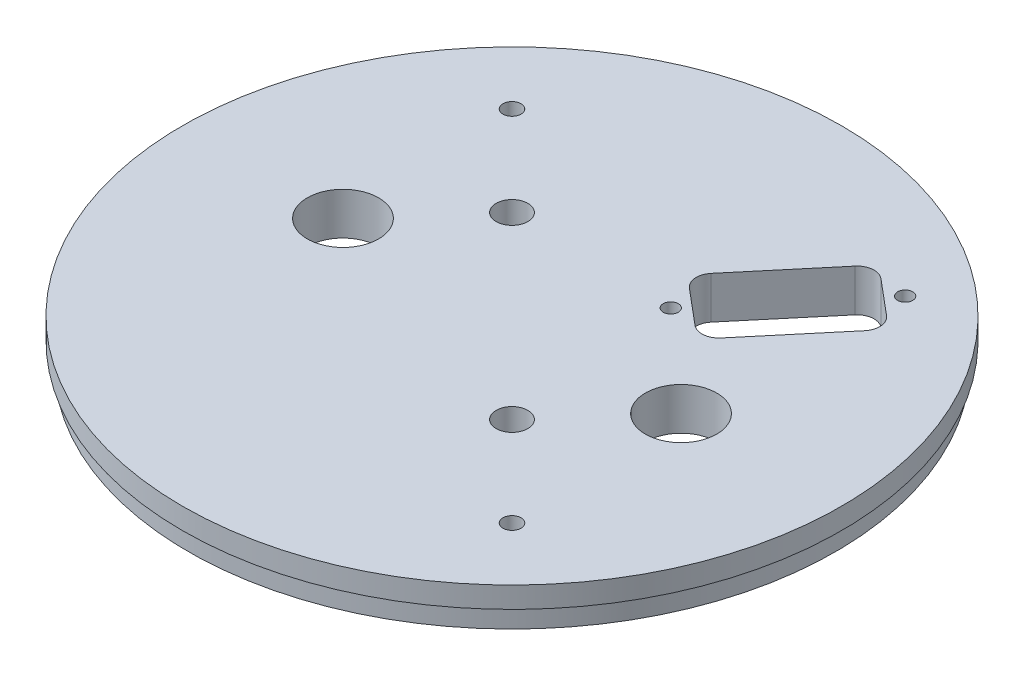
SolidWorks part; units mm, degrees
material "6061-T6 (SS)"
ref_plane "Front Plane" through (0, 0, 0) normal (0, 0, 1) x (1, 0, 0)
ref_plane "Top Plane" through (0, 0, 0) normal (0, 1, 0) x (1, 0, 0)
ref_plane "Right Plane" through (0, 0, 0) normal (1, 0, 0) x (0, 0, -1)
sketch "Sketch1" plane through (0, 0, 0) normal (0, 1, 0) x (1, 0, 0)
  line L0 (0, -49.5173) -> (0, 49.5173) construction
  line L1 (-49.5173, 0) -> (49.5173, 0) construction
  line L2 (-26.9408, 26.9408) -> (0, 0) construction
  line L3 (0, 56.7387) -> (0, 29.6936) construction
  line L4 (3.6407, 56.7387) -> (3.6407, 29.6936) construction
  line L5 (-3.6407, 56.7387) -> (-3.6407, 29.6936) construction
  line L6 (0, -56.7387) -> (0, -29.6936) construction
  line L7 (3.6407, -56.7387) -> (3.6407, -29.6936) construction
  line L8 (-3.6407, -56.7387) -> (-3.6407, -29.6936) construction
  line L9 (-35.014, -35.014) -> (54.3236, 54.3236) construction
  circle A0 centre (0, 0) radius 49.5173
  circle A1 centre (0, 0) radius 3.175 construction
  circle A2 centre (25.4, 0) radius 5.3578
  circle A3 centre (-25.4, 0) radius 5.3578
  circle A4 centre (-26.9408, 26.9408) radius 1.3589
  arc A6 (3.6407, 56.7387) -> (-3.6407, 56.7387) centre (0, 56.7387) ccw construction
  arc A7 (-3.6407, 29.6936) -> (3.6407, 29.6936) centre (0, 29.6936) ccw construction
  arc A8 (3.6407, -56.7387) -> (-3.6407, -56.7387) centre (0, -56.7387) cw construction
  arc A9 (-3.6407, -29.6936) -> (3.6407, -29.6936) centre (0, -29.6936) cw construction
  circle A10 centre (26.9408, -26.9408) radius 1.3589
  circle A11 centre (-13.4704, 13.4704) radius 2.3813
  circle A12 centre (13.4704, -13.4704) radius 2.3813
  point P16 (0, 43.2162)
  point P19 (0, 0)
  point P26 (0, -43.2162)
  dimension "D1" = 99.0346
  dimension "D2" = 6.35
  dimension "D3" = 10.7156
  dimension "D5" = 2.7178
  dimension "D8" = 4.7625
  dimension "D6" = 38.1
  dimension "D7" = 45
  dimension "D4" = 45
  dimension "D9" = 25.4
extrude "Boss-Extrude1" add sketch "Sketch1" along normal blind 6.35
sketch "Sketch2" plane through (0, 0, 0) normal (0, -1, 0) x (1, 0, 0)
  circle A0 centre (0, 0) radius 49.5173
  circle A1 centre (0, 0) radius 48.641
  dimension "D1" = 99.0346
  dimension "D2" = 97.282
extrude "Cut-Extrude1" cut sketch "Sketch2" against normal blind 3.175
sketch "Sketch3" plane through (0, 6.35, 0) normal (0, 1, 0) x (1, 0, 0)
  line L0 (0, 49.5173) -> (0, -49.5173) construction
  line L1 (-49.5173, 0) -> (49.5173, 0) construction
  line L2 (0, 34.798) -> (0, 13.97) construction
  line L3 (3.2385, 34.798) -> (3.2385, 13.97)
  line L4 (-3.2385, 34.798) -> (-3.2385, 13.97)
  line L5 (0, -34.798) -> (0, -13.97) construction
  line L6 (3.2385, -34.798) -> (3.2385, -13.97)
  line L7 (-3.2385, -34.798) -> (-3.2385, -13.97)
  circle A0 centre (0, 0) radius 49.5173 construction
  arc A1 (3.2385, 34.798) -> (-3.2385, 34.798) centre (0, 34.798) ccw
  arc A2 (-3.2385, 13.97) -> (3.2385, 13.97) centre (0, 13.97) ccw
  arc A3 (3.2385, -34.798) -> (-3.2385, -34.798) centre (0, -34.798) cw
  arc A4 (-3.2385, -13.97) -> (3.2385, -13.97) centre (0, -13.97) cw
  point P7 (0, 13.97)
  point P8 (0, 34.798)
  point P12 (0, 24.384)
  point P20 (0, -24.384)
  point P25 (0, -34.798)
  point P26 (0, -13.97)
  dimension "D1" = 13.97
  dimension "D2" = 20.828
  dimension "D3" = 6.477
extrude "Cut-Extrude2" cut sketch "Sketch3" against normal blind 3.556 from offset 5.969 offset against normal yes
hole_wizard "Tap Drill for #4-40 Tap1" positions "Sketch5" profile "Sketch6" hole size "#4-40" standard "ANSI Inch" end condition through all
sketch "Sketch5" plane through (0, 6.35, 0) normal (0, 1, 0) x (1, 0, 0)
  line L0 (0, 0) -> (53.6567, 63.9455) construction
  line L2 (0, 0) -> (25.4, 0) construction
  point P0 (10.8845, 12.9717)
  point P2 (26.9542, 32.1228)
  dimension "D1" = 50
  dimension "D2" = 25
  dimension "D3" = 16.9333
sketch "Sketch6" plane through (10.8845, 6.35, -12.9717) normal (1, 0, 0) x (0, 0, 1)
  line L0 (0, 0) -> (0, 6.35)
  line L1 (0, 6.35) -> (1.1303, 6.35)
  line L2 (1.1303, 6.35) -> (1.1303, 0)
  line L5 (1.1303, 0) -> (0, 0)
  line L11 (0, -6.35) -> (0, 107.95) construction
  dimension "Thru Hole Dia." = 2.2606
  dimension "Thru Hole Depth" = 6.35
sketch "Sketch4" plane through (0, 6.35, 0) normal (0, 1, 0) x (1, 0, 0)
  line L0 (9.7272, 16.927) -> (14.9807, 12.5187)
  line L1 (9.4141, 20.5054) -> (19.2796, 32.2627)
  line L2 (18.5591, 12.8318) -> (28.4247, 24.5891)
  line L3 (22.858, 32.5757) -> (28.1116, 28.1675)
  line L4 (0, 0) -> (26.9542, 32.1228) construction
  circle A1 centre (10.8845, 12.9717) radius 1.1303 construction
  arc A2 (19.2796, 32.2627) -> (22.858, 32.5757) centre (21.2254, 30.63) cw
  arc A3 (28.4247, 24.5891) -> (28.1116, 28.1675) centre (26.4789, 26.2217) ccw
  arc A4 (14.9807, 12.5187) -> (18.5591, 12.8318) centre (16.6134, 14.4645) ccw
  arc A5 (9.4141, 20.5054) -> (9.7272, 16.927) centre (11.3599, 18.8727) ccw
  point P11 (12.3539, 14.7229)
  dimension "D4" = 2.54
  dimension "D1" = 2.286
  dimension "D2" = 2.286
  dimension "D3" = 11.938
extrude "Cut-Extrude3" cut sketch "Sketch4" against normal through all
equation "\"leadDist\"= \"Lead_Screw_Dist\""
equation "\"Lead_Screw_Dist\" = 2in"
equation "\"D9@Sketch1\"=\"Lead_Screw_Dist\"/2"
equation "\"Lead_Screw_Diam\" = 0.375in"
equation "\"D3@Sketch1\"=\"Lead_Screw_Hole_Diam\""
equation "\"DB9_Hole_Dist\" = 25mm"
equation "\"Airbrakes_Wire_Hole_Dia\" = .25in"
equation "\"Mid_Coupler_Length\" = 13in"
equation "\"D2@Sketch5\"=\"DB9_Hole_Dist\""
equation "\"DB9_Relief_Width\" = 0.47in"
equation "\"DB9_Relief_Hole_Offset\" = 0.09in"
equation "\"D1@Sketch4\"=\"DB9_Relief_Hole_Offset\""
equation "\"D2@Sketch4\"=\"DB9_Relief_Hole_Offset\""
equation "\"D3@Sketch4\"=\"DB9_Relief_Width\""
equation "\"Body_Tube_OD\"= 4.024in"
equation "\"Body_Tube_ID\"= 3.90in"
equation "\"Coupler_OD\" = 3.899in"
equation "\"Coupler_ID\" = 3.755in"
equation "\"Avionics_Bulkhead_Thickness\" = 0.25in"
equation "\"Avionics_Bulkhead_Lip\" = 0.125in"
equation "\"Lead_Screw_Hole_Diam\" = (27/64)*1in"
equation "\"Lead_Screw_Length\" = \"Mid_Coupler_Length\" + 2*0.375in + 2*0.5in"
equation "\"D1@Sketch1\"=\"Coupler_OD\""
equation "\"D1@Sketch2\"=\"Coupler_OD\""
equation "\"D1@Cut-Extrude1\"=\"Avionics_Bulkhead_Lip\""
equation "\"D1@Boss-Extrude1\"=\"Avionics_Bulkhead_Thickness\""
